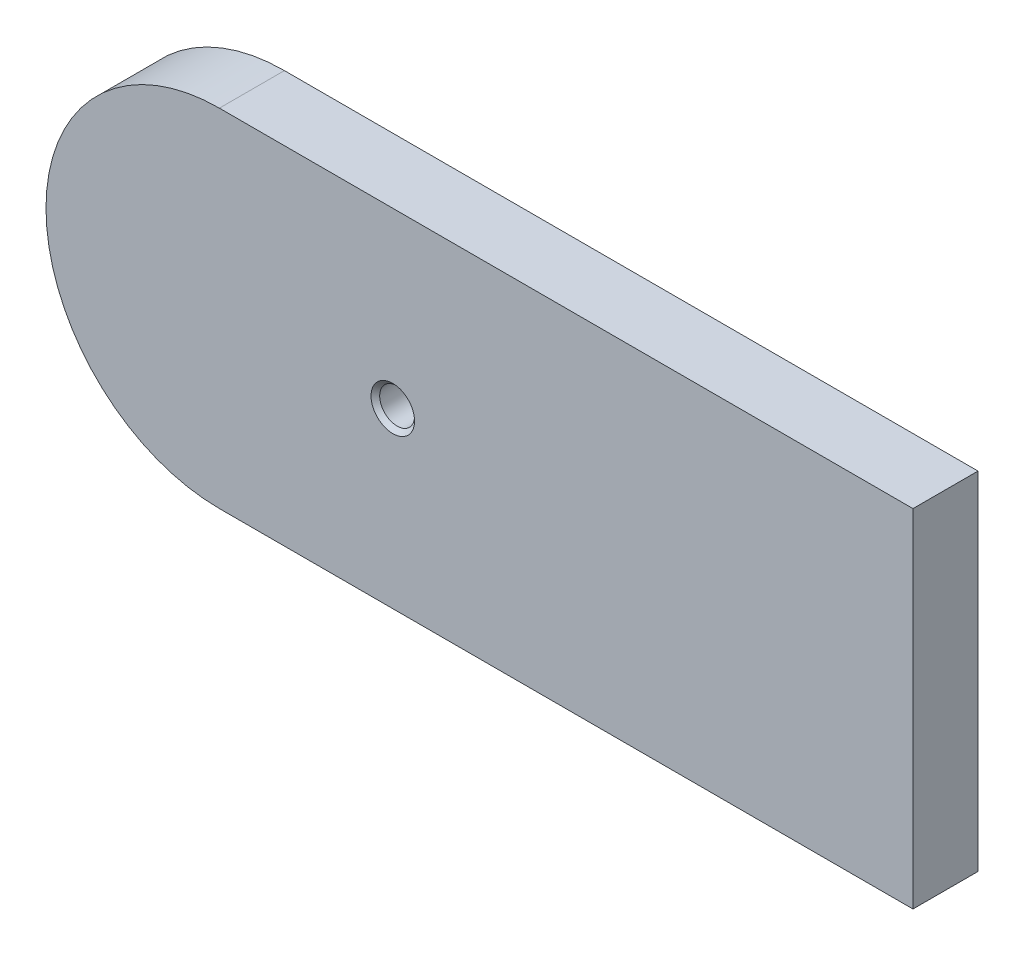
SolidWorks part; units mm, degrees
ref_plane "Front Plane" through (0, 0, 0) normal (0, 0, 1) x (1, 0, 0)
ref_plane "Top Plane" through (0, 0, 0) normal (0, 1, 0) x (1, 0, 0)
ref_plane "Right Plane" through (0, 0, 0) normal (1, 0, 0) x (0, 0, -1)
sketch "Sketch1" plane through (0, 0, 0) normal (0, 0, 1) x (1, 0, 0)
  line L1 (-76.2, 25.4) -> (76.2, 25.4)
  line L2 (-76.2, 25.4) -> (-76.2, -25.4)
  line L3 (-76.2, -25.4) -> (76.2, -25.4)
  line L4 (76.2, 25.4) -> (76.2, -25.4)
extrude "Boss-Extrude2" add sketch "Sketch1" along normal blind 9.525
hole_wizard "1/4-20 Tapped Hole1" positions "Sketch3" profile "Sketch2" tap size "1/4-20" standard "ANSI Inch" end condition through all
sketch "Sketch3" plane through (0, 0, 9.525) normal (0, 0, 1) x (1, 0, 0)
  line L0 (-76.2, 25.4) -> (-76.2, -25.4) construction
  line L1 (-76.2, -25.4) -> (76.2, -25.4) construction
  point P0 (-25.4, 0)
  dimension "D1" = 50.8
  dimension "D2" = 25.4
sketch "Sketch2" plane through (-25.4, 0, 9.525) normal (1, 0, 0) x (0, -1, 0)
  line L0 (0, 0) -> (0, 9.525)
  line L1 (0, 9.525) -> (3.1877, 9.525)
  line L2 (2.5527, 8.89) -> (2.5527, 0.635)
  line L3 (2.5527, 0.635) -> (3.1877, 0)
  line L5 (3.1877, 0) -> (0, 0)
  line L6 (-2.5527, 0.635) -> (-3.1877, 0) construction
  line L7 (3.1877, 9.525) -> (2.5527, 8.89)
  line L8 (-3.1877, 9.525) -> (-2.5527, 8.89) construction
  line L11 (0, -6.35) -> (0, 107.95) construction
  dimension "Thread Major Dia." = 5.1054
  dimension "Thru Tap Drill Depth" = 9.525
  dimension "Near C'Sink Dia." = 6.3754
  dimension "Near C'Sink Angle" = 90
  dimension "Far C'Sink Dia." = 6.3754
  dimension "Far C'Sink Angle" = 90
sketch "Sketch4" plane through (0, 0, 9.525) normal (0, 0, 1) x (1, 0, 0)
  line L0 (-76.2, -25.4) -> (76.2, -25.4) construction
  line L1 (76.2, 25.4) -> (-76.2, 25.4) construction
  arc A0 (-50.8, -25.4) -> (-50.8, 25.4) centre (-50.8, 0) cw
extrude "Cut-Extrude1" cut sketch "Sketch4" against normal through all and the other way through all
sketch "Sketch5" plane through (0, 0, 9.525) normal (0, 0, 1) x (1, 0, 0)
  line L0 (50.8, -51.7982) -> (50.8, 47.4277)
  line L1 (76.2, -25.4) -> (76.2, 25.4) construction
  dimension "D1" = 25.4
extrude "Cut-Extrude2" cut sketch "Sketch5" against normal through all and the other way through all flip side to cut
